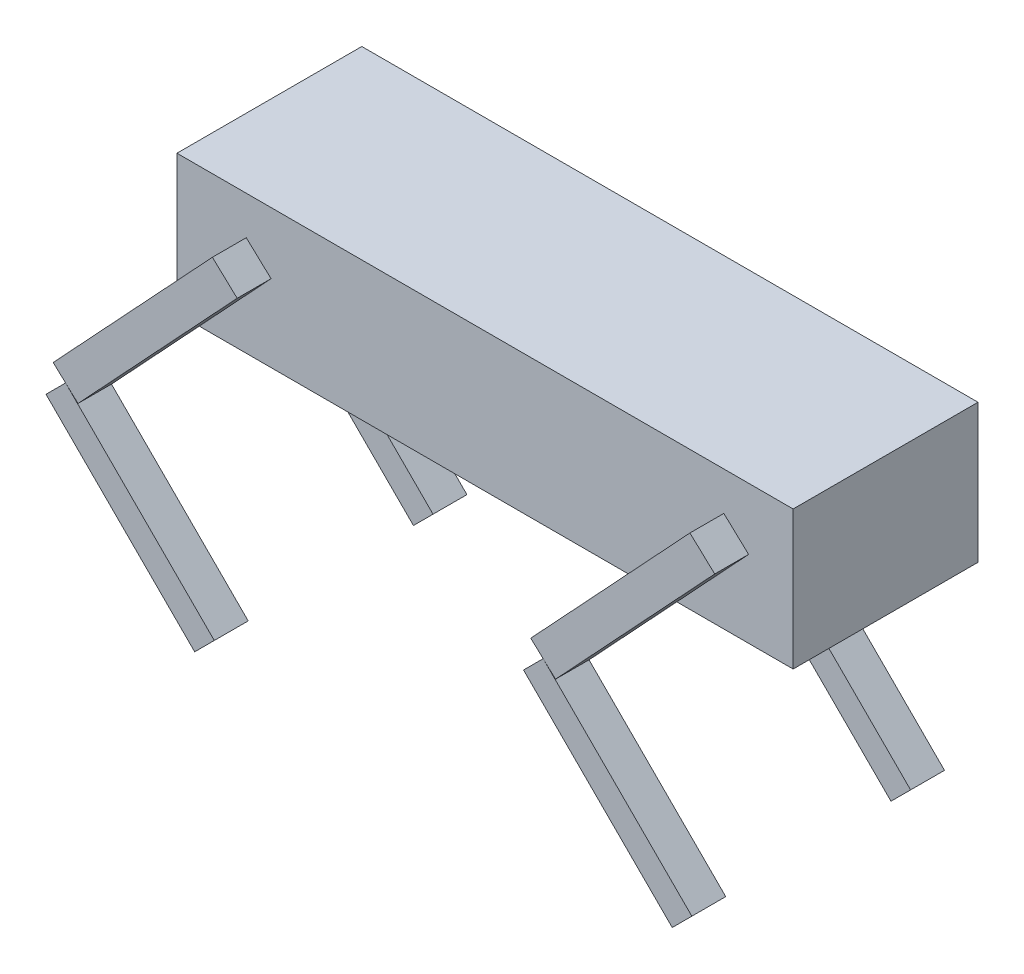
SolidWorks part; units mm, degrees
other "Markup1"
sketch "Sketch3"
ref_plane "Ebene vorne" through (0, 0, 0) normal (0, 0, 1) x (1, 0, 0)
ref_plane "Ebene oben" through (0, 0, 0) normal (0, 1, 0) x (1, 0, 0)
ref_plane "Ebene rechts" through (0, 0, 0) normal (1, 0, 0) x (0, 0, -1)
sketch "Sketch1" plane through (0, 0, 0) normal (0, 0, 1) x (1, 0, 0)
  line L1 (200, -45) -> (-200, -45)
  line L2 (200, -45) -> (200, 45)
  line L3 (200, 45) -> (-200, 45)
  line L4 (-200, -45) -> (-200, 45)
  line L5 (200, -45) -> (-200, 45) construction
  line L6 (200, 45) -> (-200, -45) construction
  point P0 (0, 0)
  dimension "D1" = 400
  dimension "D2" = 90
extrude "Boss-Extrude1" add sketch "Sketch1" along normal blind 120
sketch "Sketch2" plane through (0, 0, 120) normal (0, 0, 1) x (1, 0, 0)
  line L0 (155, 0) -> (-155, 0) construction
  line L1 (-155, 0) -> (-155, -141.4065) construction
  line L2 (155, 0) -> (155, -155.8774) construction
  line L3 (-155, 20) -> (-258.3228, -90.8001)
  line L4 (-155, 20) -> (-138.9102, 4.996)
  line L5 (-258.3228, -90.8001) -> (-242.233, -105.804)
  line L6 (-138.9102, 4.996) -> (-242.233, -105.804)
  line L7 (155, 20) -> (51.6772, -90.8001)
  line L8 (155, 20) -> (171.0898, 4.996)
  line L9 (51.6772, -90.8001) -> (67.767, -105.804)
  line L10 (171.0898, 4.996) -> (67.767, -105.804)
  line L11 (-250.2779, -98.3021) -> (-153.7578, -194.8221)
  line L12 (-250.2779, -98.3021) -> (-263.0058, -111.03)
  line L13 (-153.7578, -194.8221) -> (-166.4857, -207.5501)
  line L14 (-263.0058, -111.03) -> (-166.4857, -207.5501)
  line L15 (59.7221, -98.3021) -> (156.2422, -194.8221)
  line L16 (59.7221, -98.3021) -> (46.9942, -111.03)
  line L17 (156.2422, -194.8221) -> (143.5143, -207.5501)
  line L18 (46.9942, -111.03) -> (143.5143, -207.5501)
  point P4 (0, 0)
  line M12 (-200, -45) -> (200, -45)
  dimension "D1" = 310
  dimension "D2" = 151.5
  dimension "D3" = 47
  dimension "D4" = 151.5
  dimension "D5" = 47
  dimension "D6" = 92
  dimension "D7" = 136.5
  dimension "D8" = 18
  dimension "D9" = 22
  dimension "D10" = 22
  dimension "D11" = 92
  dimension "D12" = 136.5
  dimension "D13" = 18
  dimension "D14" = 20
  dimension "D15" = 20
extrude "Boss-Extrude2" add sketch "Sketch2" along normal blind 22 separate body contours L6 L3 L5 M12 | L12 L14 L13 L11 | L16 L18 L17 L15 | L10 L8 L7 L9 M12 | L6 L4 L3 M12 | L8 L7 M12 region at (-198.6165, -42.902, 120) region at (101.6182, -152.9261, 120) region at (135.734, -16.0879, 120) region at (85.1162, -71.827, 120) region at (-208.3818, -152.9261, 120)
extrude "Boss-Extrude3" add sketch "Sketch2<3>" against normal blind 22 from surface contours L10 L8 L7 L9 M12 | L12 L14 L13 L11 | L6 L3 L5 M12 | L16 L18 L17 L15 | L8 L7 M12 | L6 L4 L3 M12 region at (-198.6165, -42.902, 120) region at (101.6182, -152.9261, 120) region at (135.734, -16.0879, 120) region at (85.1162, -71.827, 120) region at (-208.3818, -152.9261, 120) starting at face at (0, 0, 0)
sketch "Sketch2<3>" plane through (0, 0, 120) normal (0, 0, 1) x (1, 0, 0) same geometry as "Sketch2"
sketch "Sketch4" plane through (0, 0, 120) normal (0, 0, 1) x (1, 0, 0)
  line L1 (-200, 45) -> (200, 45) construction
  line L2 (-241.0951, -28.9399) -> (125.5716, -28.9399) construction
  dimension "D1" = 400
